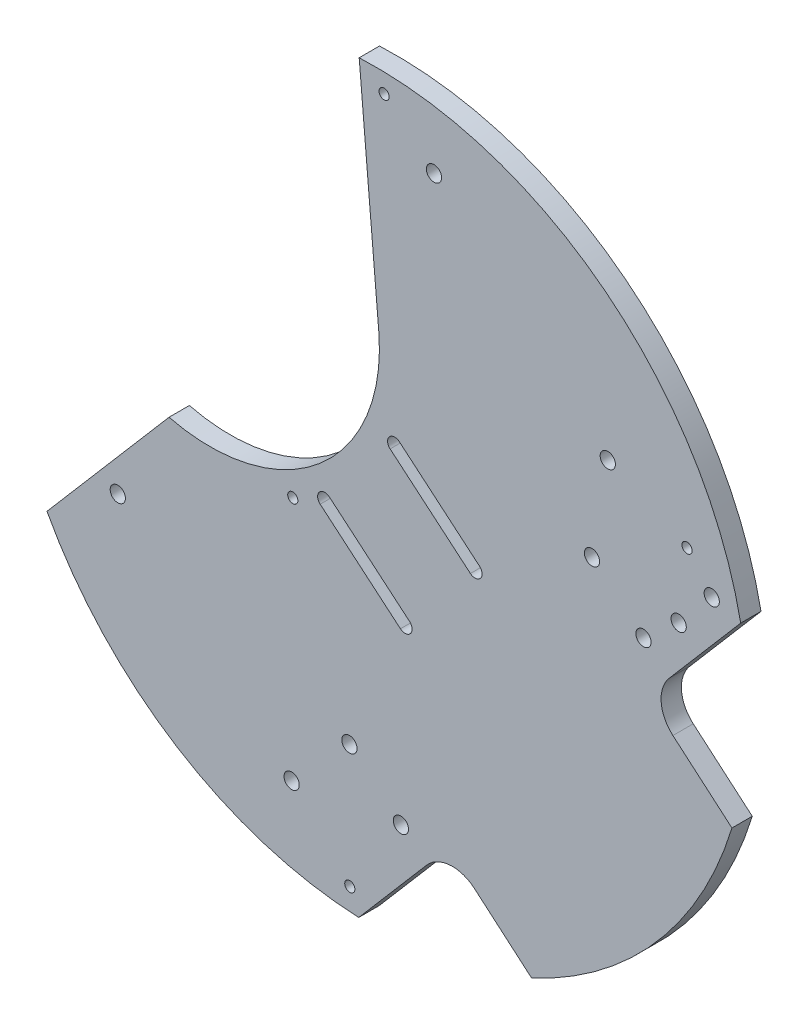
SolidWorks part; units mm, degrees
ref_plane "Front Plane" through (0, 0, 0) normal (0, 0, 1) x (1, 0, 0)
ref_plane "Top Plane" through (0, 0, 0) normal (0, 1, 0) x (1, 0, 0)
ref_plane "Right Plane" through (0, 0, 0) normal (1, 0, 0) x (0, 0, -1)
sketch "Sketch1" plane through (0, 0, 0) normal (0, 0, 1) x (1, 0, 0)
  line L0 (-65.0357, 1.7119) -> (-29.0137, 43.7635)
  line L1 (27.0989, 163.6983) -> (32.8912, 96.5787)
  arc A5 (-65.0357, 1.7119) -> (27.0989, 163.6983) centre (31.8495, 53.8009) ccw
  arc A6 (-29.0137, 43.7635) -> (32.8912, 96.5787) centre (-16.9236, 92.2798) ccw
  circle A7 centre (-44.1307, 16.5884) radius 2.25
  circle A8 centre (7.1608, -31.0475) radius 2.25
  circle A9 centre (100.4703, 97.5518) radius 2.25
  circle A10 centre (49.1788, 145.1877) radius 2.25
  dimension "D1" = 220
  dimension "D2" = 100
  dimension "D6" = 4.5
  dimension "D3" = 60.8633
  dimension "D4" = 55.3707
  dimension "D5" = 67.1195
extrude "Boss-Extrude1" add sketch "Sketch1" along normal blind 6
sketch "Sketch2" plane through (0, 0, 6) normal (0, 0, 1) x (1, 0, 0)
  line L0 (61.2734, 49.8977) -> (37.5872, 69.8968) construction
  line L1 (59.9186, 48.2932) -> (36.2324, 68.2923)
  line L2 (62.6282, 51.5023) -> (38.942, 71.5014)
  line L3 (40.6292, 25.4474) -> (16.943, 45.4465) construction
  line L4 (39.2744, 23.8429) -> (15.5882, 43.842)
  line L5 (41.984, 27.052) -> (18.2978, 47.0511)
  line L6 (61.2734, 49.8977) -> (46.5625, 32.4747) construction
  line L7 (46.5625, 32.4747) -> (37.9334, 22.2547) construction
  line L8 (15.0411, 41.8646) -> (37.8247, 22.3478) construction
  line L9 (50.2278, 38.2835) -> (29.8022, 55.5295) construction
  line L11 (16.943, 45.4465) -> (37.5872, 69.8968) construction
  arc A0 (59.9186, 48.2932) -> (62.6282, 51.5023) centre (61.2734, 49.8977) ccw
  arc A1 (38.942, 71.5014) -> (36.2324, 68.2923) centre (37.5872, 69.8968) ccw
  arc A2 (39.2744, 23.8429) -> (41.984, 27.052) centre (40.6292, 25.4474) ccw
  arc A3 (18.2978, 47.0511) -> (15.5882, 43.842) centre (16.943, 45.4465) ccw
  circle A5 centre (58.207, 52.2904) radius 2.25 construction
  point P4 (49.4303, 59.8973)
  point P9 (28.7861, 35.447)
  dimension "D1" = 4.2
  dimension "D2" = 4.2
  dimension "D3" = 25
  dimension "D4" = 16
  dimension "D5" = 32
  dimension "D6" = 31
  dimension "D7" = 31
  dimension "D8" = 16
extrude "Cut-Extrude1" cut sketch "Sketch2" against normal blind 10
hole_wizard "Ø4.5 (4.5) Diameter Hole" positions "Sketch3" profile "Sketch4" hole size "Ø4.5" standard "IS"
sketch "Sketch3" plane through (207.2158, -96.42, 6) normal (0, 0, 1) x (-0.6506, -0.7595, 0)
  point P0 (80.5001, -194.4616)
  point P3 (77.6909, -264.4052)
  point P6 (-80.6779, -277.2022)
  point P9 (-77.8687, -207.2586)
sketch "Sketch4" plane through (7.1608, -31.0475, 6) normal (1, 0, 0) x (0, -1, 0)
  line L0 (0, 0) -> (0, 11.3519)
  line L1 (0, 11.3519) -> (2.25, 10)
  line L2 (2.25, 10) -> (2.25, 0)
  line L3 (2.25, 0) -> (0, 0)
  line L4 (0, 11.3519) -> (-2.25, 10) construction
  line L5 (0, -6.35) -> (0, 107.95) construction
  dimension "Hole Dia." = 4.5
  dimension "Hole Depth" = 10
  dimension "Drill Angle" = 118
hole_wizard "Ø3.0mm Dowel Hole1" positions "Sketch5" profile "Sketch6" hole size "Ø3.0" standard "IS" end condition through all
sketch "Sketch5" plane through (207.2158, -96.42, 6) normal (0, 0, 1) x (-0.6506, -0.7595, 0)
  point P0 (-80.9158, -296.795)
  point P3 (-84.9452, -182.5189)
  point P6 (25.2163, -241.3641)
  point P9 (83.3286, -169.4245)
sketch "Sketch6" plane through (34.4537, 158.1146, 6) normal (1, 0, 0) x (0, -1, 0)
  line L0 (0, 0) -> (0, 6)
  line L1 (0, 6) -> (1.5, 6)
  line L2 (1.5, 6) -> (1.5, 0)
  line L3 (1.5, 0) -> (0, 0)
  line L4 (0, -6.35) -> (0, 107.95) construction
  dimension "Thru Hole Dia." = 3
  dimension "Thru Hole Depth" = 6
sketch "Sketch7" plane through (0, 0, 6) normal (0, 0, 1) x (1, 0, 0)
  line L0 (139.6892, 75.4943) -> (26.9717, -56.0909) construction
  line L2 (37.8247, 22.3478) -> (46.282, 32.2207) construction
  line L3 (139.6892, 75.4943) -> (118.5944, 50.8684)
  line L4 (119.6834, 36.7683) -> (137.1053, 21.8444)
  line L5 (84.7002, 70.5146) -> (146.9827, 12.671) construction
  line L6 (137.1053, 21.8444) -> (157.1792, 45.2784)
  line L7 (157.1792, 45.2784) -> (139.6892, 75.4943)
  line L8 (26.9717, -56.0909) -> (47.0048, -32.7045)
  line L9 (61.105, -31.6155) -> (77.9709, -46.0631)
  line L10 (23.454, 4.5684) -> (85.7366, -53.2753) construction
  line L11 (77.9709, -46.0631) -> (19.4206, -114.4141)
  line L12 (19.4206, -114.4141) -> (26.9717, -56.0909)
  line L13 (39.4103, -26.1989) -> (110.9998, 57.374) construction
  line L14 (110.9998, 57.374) -> (95.8107, 70.3852) construction
  line L15 (95.8107, 70.3852) -> (24.2212, -13.1877) construction
  line L16 (24.2212, -13.1877) -> (39.4103, -26.1989) construction
  line L17 (121.3842, 66.4224) -> (131.1426, 77.8142) construction
  arc A0 (-65.0357, 1.7119) -> (27.0989, 163.6983) centre (31.8495, 53.8009) ccw construction
  circle A2 centre (34.4537, 158.1146) radius 1.6 construction
  arc A3 (118.5944, 50.8684) -> (119.6834, 36.7683) centre (126.1889, 44.3629) ccw
  arc A4 (47.0048, -32.7045) -> (61.105, -31.6155) centre (54.5994, -39.2101) cw
  circle A5 centre (39.4103, -26.1989) radius 2.25
  circle A6 centre (110.9998, 57.374) radius 2.25
  circle A7 centre (24.2212, -13.1877) radius 2.25
  circle A8 centre (95.8107, 70.3852) radius 2.25
  circle A9 centre (121.3842, 66.4224) radius 2.25
  circle A10 centre (131.1426, 77.8142) radius 2.25
  point P22 (112.0888, 43.2739)
  point P25 (53.5104, -25.1099)
  dimension "D8" = 10
  dimension "D9" = 4.5
  dimension "D1" = 214.3362
  dimension "D2" = 90
  dimension "D3" = 90
  dimension "D4" = 90
  dimension "D5" = 30.8563
  dimension "D6" = 90
  dimension "D7" = 90
  dimension "D10" = 20
  dimension "D11" = 10
  dimension "D12" = 10
  dimension "D13" = 10
  dimension "D14" = 8
  dimension "D15" = 15
  dimension "D16" = 15.5539
extrude "Cut-Extrude2" cut sketch "Sketch7" against normal blind 10
